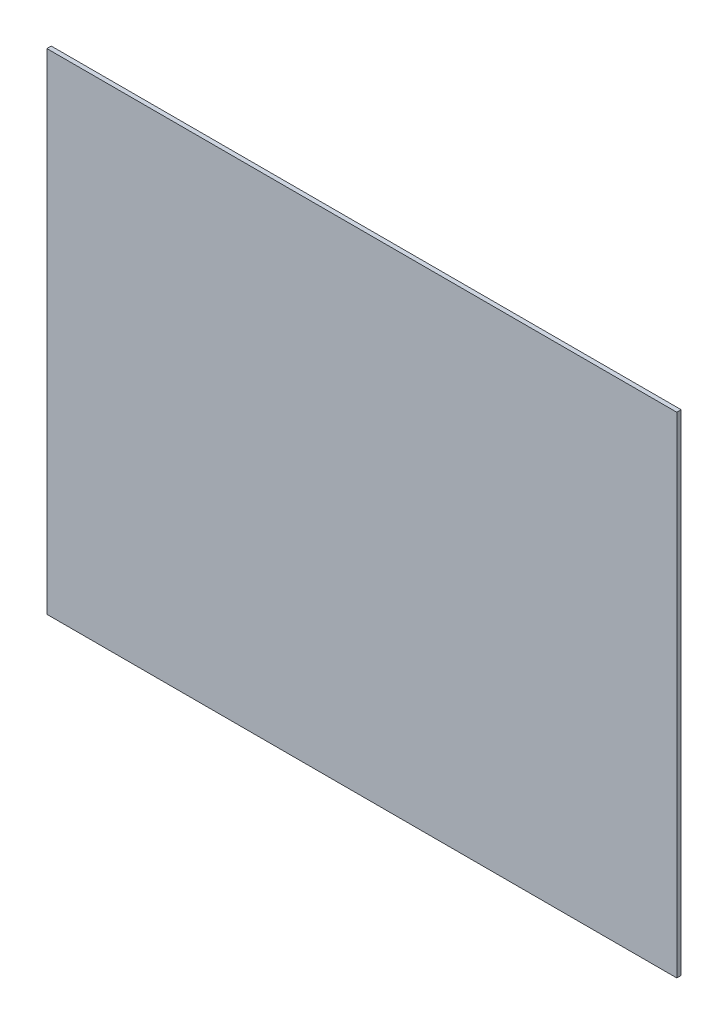
SolidWorks part; units mm, degrees
ref_plane "Front Plane" through (0, 0, 0) normal (0, 0, 1) x (1, 0, 0)
ref_plane "Top Plane" through (0, 0, 0) normal (0, 1, 0) x (1, 0, 0)
ref_plane "Right Plane" through (0, 0, 0) normal (1, 0, 0) x (0, 0, -1)
sketch "Sketch1" plane through (0, 0, 0) normal (0, 0, 1) x (1, 0, 0)
  line L1 (-457.2, -355.6) -> (457.2, -355.6)
  line L2 (-457.2, -355.6) -> (-457.2, 355.6)
  line L3 (-457.2, 355.6) -> (457.2, 355.6)
  line L4 (457.2, -355.6) -> (457.2, 355.6)
  line L5 (-457.2, -355.6) -> (457.2, 355.6) construction
  line L6 (-457.2, 355.6) -> (457.2, -355.6) construction
  point P0 (0, 0)
  dimension "D1" = 914.4
  dimension "D2" = 711.2
extrude "Boss-Extrude1" add sketch "Sketch1" along normal blind 6.35
